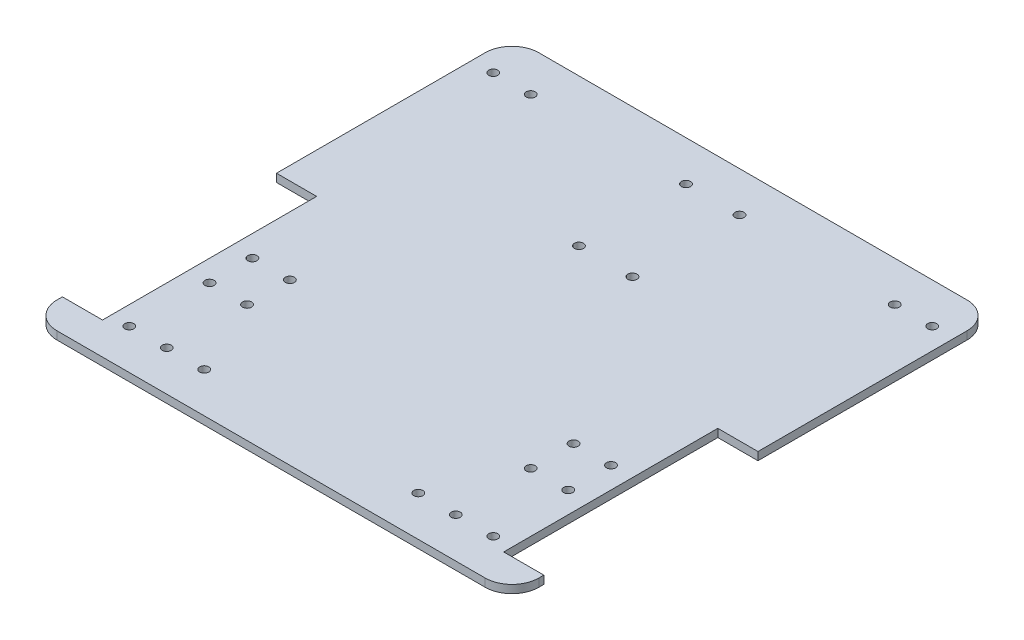
SolidWorks part; units mm, degrees
ref_plane "Front Plane" through (0, 0, 0) normal (0, 0, 1) x (1, 0, 0)
ref_plane "Top Plane" through (0, 0, 0) normal (0, 1, 0) x (1, 0, 0)
ref_plane "Right Plane" through (0, 0, 0) normal (1, 0, 0) x (0, 0, -1)
sketch "Sketch1" plane through (0, 0, 0) normal (0, 1, 0) x (1, 0, 0)
  line L1 (-90, 90) -> (90, 90)
  line L2 (-90, 90) -> (-90, -90)
  line L3 (-90, -90) -> (90, -90)
  line L4 (90, 90) -> (90, -90)
  line L5 (-90, 90) -> (90, -90) construction
  line L6 (-90, -90) -> (90, 90) construction
  point P0 (0, 0)
  dimension "D1" = 180
  dimension "D2" = 180
extrude "Boss-Extrude1" add sketch "Sketch1" along normal blind 3
fillet "Fillet1" radius 10 4 edges at (-90, 1.5, -90) (-90, 1.5, 90) (90, 1.5, -90) (90, 1.5, 90)
sketch "Sketch2" plane through (0, 3, 0) normal (0, 1, 0) x (1, 0, 0)
  circle A0 centre (-82, 75) radius 1.7
  circle A1 centre (-68, 75) radius 1.7
  circle A2 centre (68, 75) radius 1.7
  circle A3 centre (82, 75) radius 1.7
  circle A4 centre (-82, -75) radius 1.7
  circle A5 centre (-68, -75) radius 1.7
  circle A6 centre (68, -75) radius 1.7
  circle A7 centre (82, -75) radius 1.7
  circle A24 centre (-67, -30) radius 1.7
  circle A25 centre (-67, -46) radius 1.7
  circle A26 centre (-53, -30) radius 1.7
  circle A27 centre (-53, -46) radius 1.7
  circle A28 centre (53, -30) radius 1.7
  circle A29 centre (53, -46) radius 1.7
  circle A30 centre (67, -30) radius 1.7
  circle A31 centre (67, -46) radius 1.7
  circle A32 centre (-54, -75) radius 1.7
  circle A33 centre (54, -75) radius 1.7
  circle A34 centre (-40, -75) radius 1.7
  circle A35 centre (40, -75) radius 1.7
  dimension "D1" = 3.4
  dimension "D10" = 30
  dimension "D11" = 14
  dimension "D13" = 14
  dimension "D14" = 14
  dimension "D17" = 3.4
  dimension "D18" = 14
  dimension "D19" = 14
  dimension "D20" = 14
  dimension "D2" = 14
  dimension "D3" = 14
  dimension "D4" = 82
  dimension "D5" = 82
  dimension "D6" = 75
  dimension "D7" = 75
  dimension "D12" = 16
  dimension "D15" = 67
  dimension "D16" = 67
extrude "Cut-Extrude1" cut sketch "Sketch2" against normal up to surface (3 mm away) up to face at (0, 0, 0)
sketch "Sketch3" plane through (0, 3, 0) normal (0, 1, 0) x (1, 0, 0)
  circle A4 centre (10, 35) radius 1.7
  circle A5 centre (-10, 35) radius 1.7
  circle A6 centre (-10, 75) radius 1.7
  circle A7 centre (10, 75) radius 1.7
  dimension "D1" = 3.4
  dimension "D6" = 20
  dimension "D8" = 40
  dimension "D9" = 35
  dimension "D7" = 10
extrude "Cut-Extrude2" cut sketch "Sketch3" against normal up to surface (3 mm away) up to face at (-67, 0, 31.7)
sketch "Sketch7" plane through (0, 3, 0) normal (0, 1, 0) x (1, 0, 0)
  line L0 (-90, 80) -> (-90, -80) construction
  line L1 (-105, 2) -> (-75, 2)
  line L2 (-105, 2) -> (-105, -78)
  line L3 (-105, -78) -> (-75, -78)
  line L4 (-75, 2) -> (-75, -78)
  line L5 (-105, 2) -> (-75, -78) construction
  line L6 (-105, -78) -> (-75, 2) construction
  line L7 (90, -80) -> (90, 80) construction
  line L8 (75, 1.9002) -> (105, 1.9002)
  line L9 (75, 1.9002) -> (75, -78.0998)
  line L10 (75, -78.0998) -> (105, -78.0998)
  line L11 (105, 1.9002) -> (105, -78.0998)
  line L12 (75, 1.9002) -> (105, -78.0998) construction
  line L13 (75, -78.0998) -> (105, 1.9002) construction
  circle A0 centre (-67, -30) radius 1.7 construction
  point P0 (-90, -38)
  point P7 (90, -38.0998)
  dimension "D1" = 80
  dimension "D2" = 15
  dimension "D3" = 8
extrude "Cut-Extrude7" cut sketch "Sketch7" against normal through all
